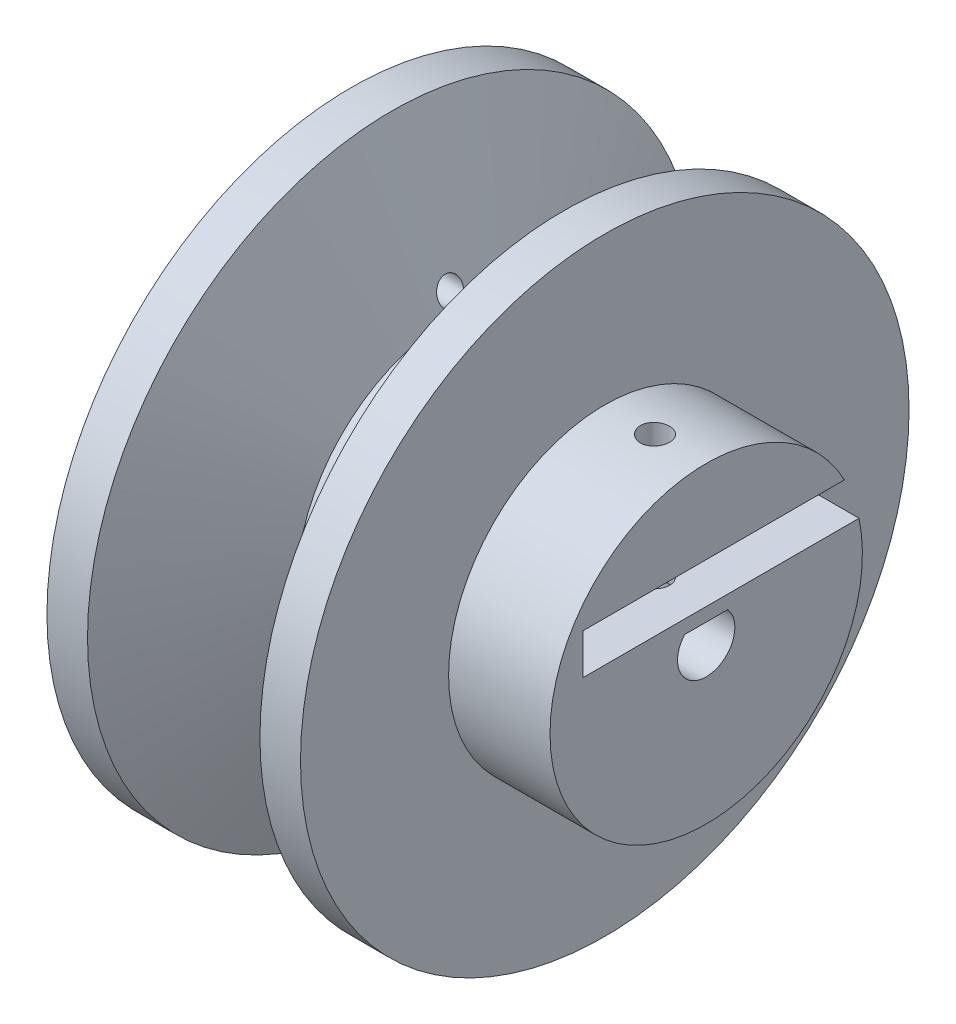
SolidWorks part; units mm, degrees
ref_plane "前基準面" through (0, 0, 0) normal (0, 0, 1) x (1, 0, 0)
ref_plane "上基準面" through (0, 0, 0) normal (0, 1, 0) x (1, 0, 0)
ref_plane "右基準面" through (0, 0, 0) normal (1, 0, 0) x (0, 0, -1)
sketch "草圖1" plane through (0, 0, 0) normal (0, 0, 1) x (1, 0, 0)
  line L0 (0, 0) -> (0, 30)
  line L1 (0, 30) -> (4, 30)
  line L2 (4, 30) -> (10, 15.4)
  line L3 (10, 15.4) -> (15, 15.4)
  line L4 (15, 15.4) -> (21, 30)
  line L5 (21, 30) -> (25, 30)
  line L6 (25, 30) -> (25, 15.4)
  line L7 (25, 15.4) -> (35, 15.4)
  line L8 (35, 15.4) -> (35, 0)
  line L9 (-743.1564, 0) -> (36475.4845, 0) construction
  line L10 (0, 0) -> (35, 0)
  dimension "D1" = 30
  dimension "D2" = 4
  dimension "D3" = 6
  dimension "D4" = 5
  dimension "D5" = 6
  dimension "D6" = 4
  dimension "D7" = 10
  dimension "D8" = 15.4
  dimension "D9" = 30
  dimension "D10" = 30
  dimension "D11" = 15.4
  dimension "D12" = 15.4
revolve "旋轉1" add sketch "草圖1" angle 360 about L9
ref_plane "平面1" through (0, 12, 0) normal (0, 1, 0) x (1, 0, 0)
sketch "草圖3" plane through (35, 0, 0) normal (1, 0, 0) x (0, 0, -1)
  circle A0 centre (0, 0) radius 2.825
  dimension "D1" = 5.65
extrude "除料-伸長2" cut sketch "草圖3" against normal blind 35
sketch "草圖14" plane through (0, 0, 0) normal (-1, 0, 0) x (0, 0, 1)
  circle A0 centre (-0.4353, 17.0039) radius 1.25
  dimension "D1" = 2.5
extrude "除料-伸長5" cut sketch "草圖14" against normal blind 12
ref_plane "平面2" through (0, 22, 0) normal (0, 1, 0) x (1, 0, 0)
sketch "草圖16" plane through (35, 0, 0) normal (1, 0, 0) x (0, 0, -1)
  line L1 (-2.61, 2.851) -> (2.3989, 2.851)
  line L2 (-2.61, 2.851) -> (-2.61, 1.851)
  line L3 (-2.61, 1.851) -> (2.3989, 1.851)
  line L4 (2.3989, 2.851) -> (2.3989, 1.851)
  dimension "D1" = 1
extrude "填料-伸長2" add sketch "草圖16" against normal blind 30
sketch "草圖19" plane through (35, 0, 0) normal (1, 0, 0) x (0, 0, -1)
  line L1 (-0.5637, 2.9297) -> (0.3954, 2.9297)
  line L2 (-0.5637, 2.9297) -> (-0.5637, 2.4182)
  line L3 (-0.5637, 2.4182) -> (0.3954, 2.4182)
  line L4 (0.3954, 2.9297) -> (0.3954, 2.4182)
extrude "填料-伸長3" add sketch "草圖19" against normal blind 30
sketch "草圖24" plane through (35, 0, 0) normal (1, 0, 0) x (0, 0, -1)
  line L1 (-12.1511, 7.1809) -> (15.0679, 7.1809)
  line L2 (-12.1511, 7.1809) -> (-12.1511, 3.1809)
  line L3 (-12.1511, 3.1809) -> (15.0679, 3.1809)
  line L4 (15.0679, 7.1809) -> (15.0679, 3.1809)
  line L5 (-12.1511, 7.1809) -> (15.0679, 3.1809) construction
  line L6 (-12.1511, 3.1809) -> (15.0679, 7.1809) construction
  circle A0 centre (0, 0) radius 15.4 construction
  point P0 (1.4584, 5.1809)
  dimension "D1" = 4
extrude "除料-伸長8" cut sketch "草圖24" against normal blind 9
sketch "草圖25" plane through (0, 22, 0) normal (0, 1, 0) x (1, 0, 0)
  circle A0 centre (29.9567, 0) radius 1.43
  dimension "D1" = 2.86
extrude "除料-伸長9" cut sketch "草圖25" against normal blind 22
ref_plane "平面3" through (0, 0, 20) normal (0, 0, 1) x (1, 0, 0)
sketch "草圖35" plane through (0, 0, 0) normal (0, 0, 1) x (1, 0, 0)
  line L0 (15, -15.4) -> (10, -15.4)
  line L1 (10, -15.4) -> (12.5, -16.5043)
  line L2 (12.5, -16.5043) -> (15, -15.4)
extrude "伸長-薄件4" add sketch "草圖35" along normal blind 3 and the other way blind 3 thin thin type one direction wall 0.5
sketch "草圖36" plane through (0, 0, 0) normal (0, 0, 1) x (1, 0, 0)
  line L0 (11.9029, -16.7872) -> (13.3431, -16.7872)
  line L1 (9.7118, -15.8193) -> (12.5, -17.0509) construction
  line L2 (13.3431, -16.7872) -> (13.3431, -17.3629)
  line L3 (13.3431, -17.3629) -> (11.8597, -17.3629)
  line L4 (11.8597, -17.3629) -> (11.9029, -16.7872)
extrude "除料-伸長12" cut sketch "草圖36" against normal blind 3 and the other way blind 3
fillet "圓角14" radius 0.5 2 edges at (11.9029, -16.7872, 0) (13.0971, -16.7872, 0) curvature continuous yes
